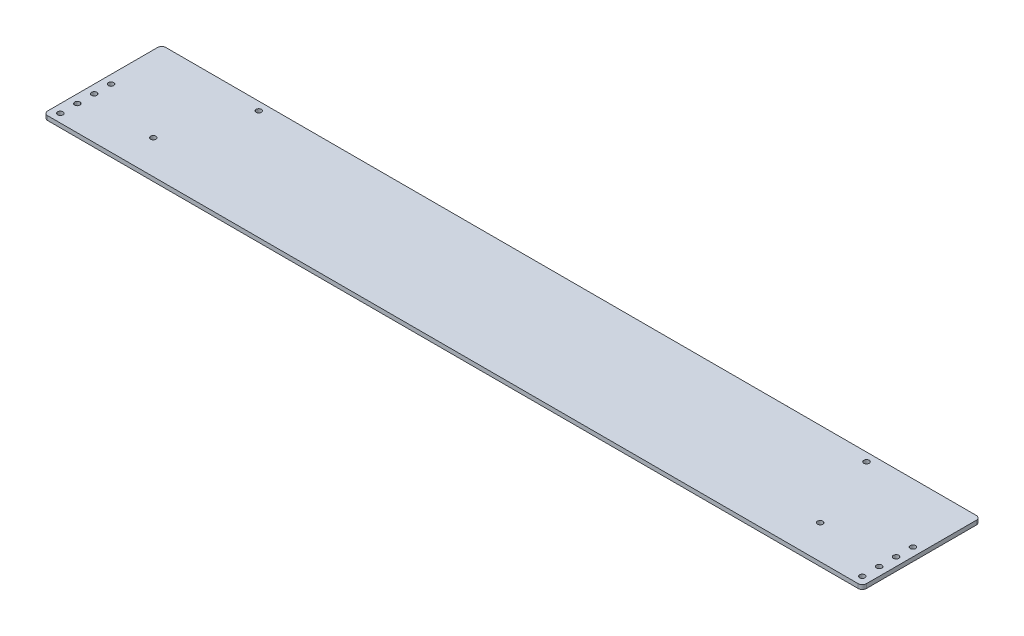
SolidWorks part; units mm, degrees
material "PC High Viscosity"
ref_plane "Front Plane" through (0, 0, 0) normal (0, 0, 1) x (1, 0, 0)
ref_plane "Top Plane" through (0, 0, 0) normal (0, 1, 0) x (1, 0, 0)
ref_plane "Right Plane" through (0, 0, 0) normal (1, 0, 0) x (0, 0, -1)
sketch "Sketch1" plane through (0, 0, 0) normal (0, 1, 0) x (1, 0, 0)
  line L0 (-301.625, 0) -> (-301.625, -38.1) construction
  line L1 (-307.975, -44.45) -> (307.975, -44.45)
  line L2 (-307.975, -44.45) -> (-307.975, 44.45)
  line L3 (-307.975, 44.45) -> (307.975, 44.45)
  line L4 (307.975, -44.45) -> (307.975, 44.45)
  line L5 (-307.975, -44.45) -> (307.975, 44.45) construction
  line L6 (-307.975, 44.45) -> (307.975, -44.45) construction
  line L7 (0, 44.45) -> (0, -44.45) construction
  circle A2 centre (-301.625, 0) radius 2.0193
  circle A3 centre (-301.625, -12.7) radius 2.0193
  circle A4 centre (-301.625, -25.4) radius 2.0193
  circle A5 centre (-301.625, -38.1) radius 2.0193
  circle A6 centre (301.625, -38.1) radius 2.0193
  circle A7 centre (301.625, -25.4) radius 2.0193
  circle A8 centre (301.625, -12.7) radius 2.0193
  circle A9 centre (301.625, 0) radius 2.0193
  point P0 (0, 0)
  dimension "D3" = 6.35
  dimension "D4" = 4.0386
  dimension "D5" = 4
  dimension "D6" = 44.45
  dimension "D7" = 12.7
  dimension "D1" = 88.9
  dimension "D2" = 615.95
extrude "Boss-Extrude1" add sketch "Sketch1" along normal blind 3.175
fillet "Fillet1" radius 3.175 4 edges at (307.975, 1.5875, 44.45) (-307.975, 1.5875, -44.45) (307.975, 1.5875, -44.45) (-307.975, 1.5875, 44.45)
sketch "Sketch2" plane through (0, 3.175, 0) normal (0, 1, 0) x (1, 0, 0)
  line L0 (304.8, 44.45) -> (-304.8, 44.45) construction
  line L1 (-307.975, 41.275) -> (-307.975, -41.275) construction
  line L2 (-304.8, -44.45) -> (304.8, -44.45) construction
  line L3 (0, 44.45) -> (0, -44.45) construction
  circle A0 centre (-228.6, 38.1) radius 2.0193
  circle A1 centre (-250.825, -19.05) radius 2.0193
  circle A2 centre (-250.825, -19.05) radius 25.4 construction
  circle A3 centre (-228.6, 38.1) radius 25.4 construction
  circle A4 centre (250.825, -19.05) radius 25.4 construction
  circle A5 centre (250.825, -19.05) radius 2.0193
  circle A6 centre (228.6, 38.1) radius 25.4 construction
  circle A7 centre (228.6, 38.1) radius 2.0193
  dimension "D1" = 4.0386
  dimension "D2" = 50.8
  dimension "D3" = 50.8
  dimension "D4" = 6.35
  dimension "D6" = 25.4
  dimension "D7" = 79.375
  dimension "D5" = 57.15
extrude "Cut-Extrude1" cut sketch "Sketch2" against normal through all
